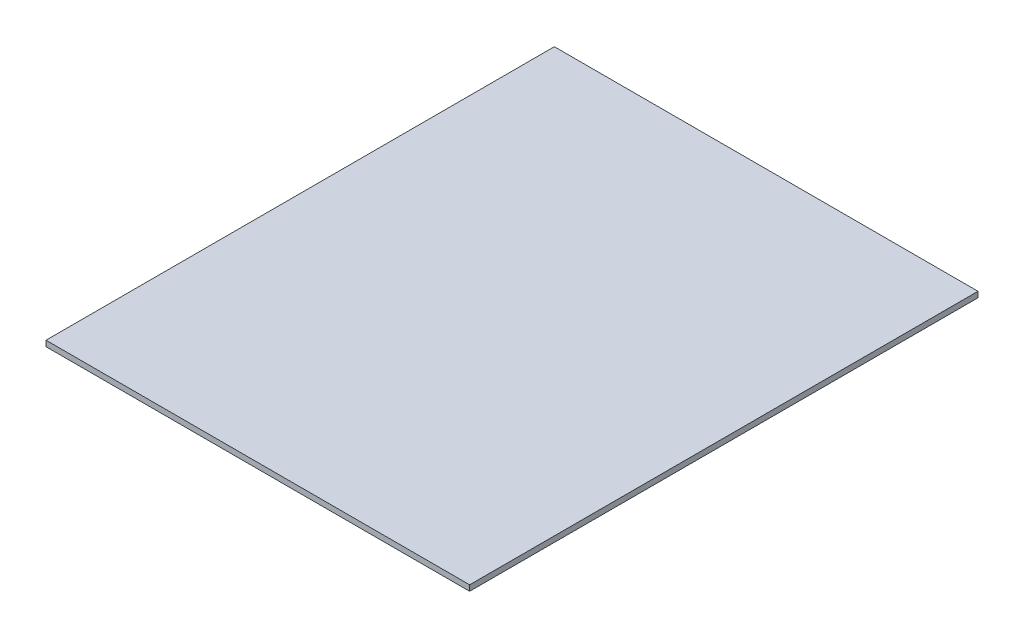
SolidWorks part; units mm, degrees
ref_plane "Front Plane" through (0, 0, 0) normal (0, 0, 1) x (1, 0, 0)
ref_plane "Top Plane" through (0, 0, 0) normal (0, 1, 0) x (1, 0, 0)
ref_plane "Right Plane" through (0, 0, 0) normal (1, 0, 0) x (0, 0, -1)
sketch "Sketch1" plane through (0, 0, 0) normal (0, 1, 0) x (1, 0, 0)
  line L1 (-70.2094, -105.9463) -> (79.7906, -105.9463)
  line L2 (-70.2094, -105.9463) -> (-70.2094, 74.0537)
  line L3 (-70.2094, 74.0537) -> (79.7906, 74.0537)
  line L4 (79.7906, -105.9463) -> (79.7906, 74.0537)
  dimension "D1" = 150
  dimension "D2" = 180
extrude "Boss-Extrude1" add sketch "Sketch1" along normal blind 2
